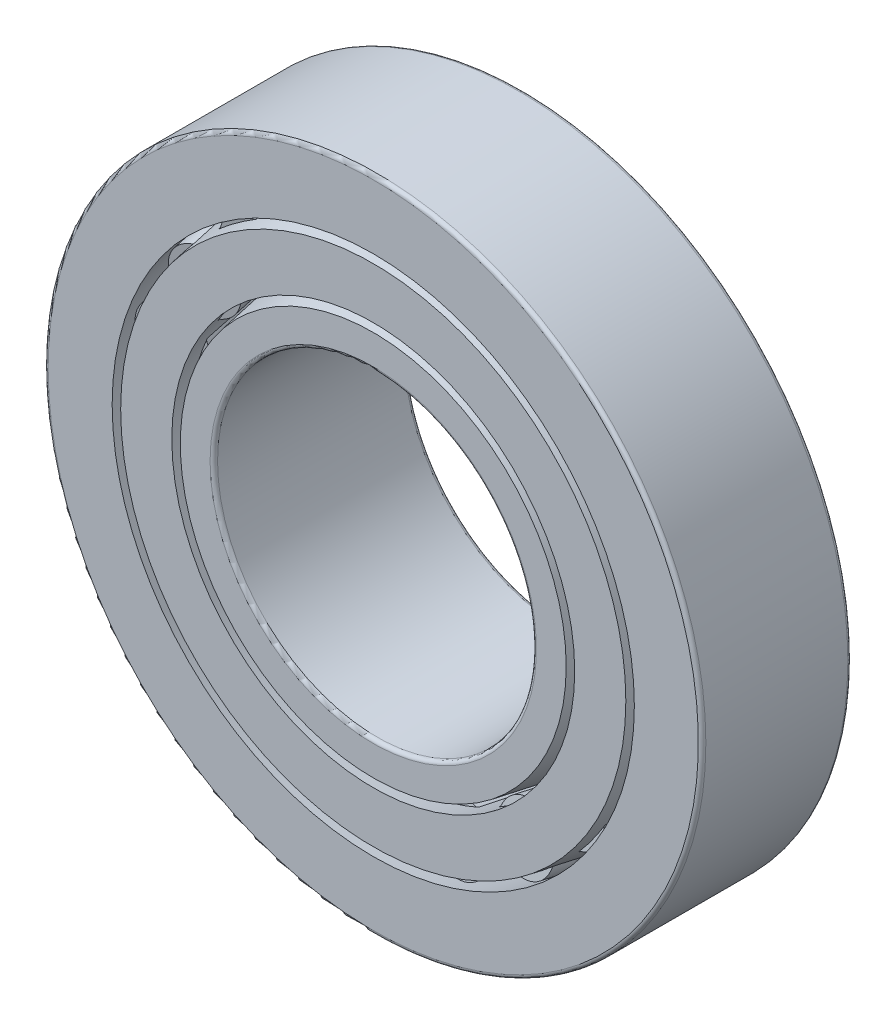
SolidWorks part; units mm, degrees
ref_plane "Front Plane" through (0, 0, 0) normal (0, 0, 1) x (1, 0, 0)
ref_plane "Top Plane" through (0, 0, 0) normal (0, 1, 0) x (1, 0, 0)
ref_plane "Right Plane" through (0, 0, 0) normal (1, 0, 0) x (0, 0, -1)
sketch "Sketch1" plane through (0, 0, 0) normal (1, 0, 0) x (0, 0, -1)
  line L0 (-15.4781, 0) -> (15.4781, 0) construction
  line L1 (0, 0) -> (0, 52.3875) construction
  line L2 (-15.4781, 25.4) -> (15.4781, 25.4) construction
  line L3 (15.4781, 25.4) -> (15.4781, 36.195) construction
  line L4 (15.4781, 36.195) -> (-15.4781, 30.7366) construction
  line L5 (-15.4781, 30.7366) -> (-15.4781, 25.4) construction
  line L7 (-15.4781, 52.3875) -> (8.3344, 52.3875)
  line L8 (8.3344, 52.3875) -> (8.3344, 45.7913)
  line L9 (8.3344, 45.7913) -> (-15.4781, 41.5925)
  line L10 (-15.4781, 41.5925) -> (-15.4781, 52.3875)
  line L11 (-15.4781, 41.5925) -> (-13.6217, 31.0639) construction
  line L12 (12.8279, 46.5836) -> (14.6844, 36.055) construction
  line L14 (-15.4781, 30.7366) -> (-13.6217, 31.0639) construction
  line L15 (-15.4781, 30.7366) -> (14.6844, 36.055) construction
  point P5 (0, 25.4)
  dimension "D1" = 100
  dimension "Width" = 30.9562
  dimension "OD" = 104.775
  dimension "Shaft Dia" = 50.8
  dimension "D2" = 26.9875
  dimension "D3" = 10.795
  dimension "Outer Wd" = 23.8125
  dimension "Bearing Wd" = 30.1625
revolve "Revolve1" add sketch "Sketch1" angle 360 about L0
sketch "Sketch5" plane through (0, 0, 0) normal (1, 0, 0) x (0, 0, -1)
  line L0 (15.4781, 36.195) -> (-15.4781, 30.7366) construction
  line L1 (15.4781, 36.195) -> (-15.4781, 30.7366)
  line L2 (-15.4781, 30.7366) -> (-15.4781, 25.4)
  line L3 (-15.4781, 25.4) -> (15.4781, 25.4)
  line L4 (15.4781, 25.4) -> (15.4781, 36.195)
revolve "Revolve4" add sketch "Sketch5" angle 360 about L0
sketch "Sketch2" plane through (0, 0, 0) normal (1, 0, 0) x (0, 0, -1)
  line L0 (-15.4781, 40.2355) -> (-15.4781, 32.0936)
  line L1 (8.3344, 44.4343) -> (13.06, 45.2675)
  line L2 (-15.4781, 32.0936) -> (8.3344, 36.2924)
  line L3 (12.8279, 46.5836) -> (14.6844, 36.055) construction
  line L4 (8.3344, 36.2924) -> (8.3344, 44.4343) construction
  line L5 (8.3344, 44.4343) -> (-15.4781, 40.2355)
  line L6 (8.3344, 45.7913) -> (-15.4781, 41.5925) construction
  line L7 (15.4781, 36.195) -> (-15.4781, 30.7366) construction
  line L8 (-15.4781, 41.5925) -> (8.3344, 45.7913) construction
  line L9 (-15.4781, 30.7366) -> (14.6844, 36.055) construction
  line L10 (13.06, 45.2675) -> (14.4523, 37.3711)
  line L11 (-15.4781, 41.5925) -> (-15.4781, 40.2355) construction
  line L12 (-15.4781, 32.0936) -> (-15.4781, 30.7366) construction
  line L13 (8.3344, 52.3875) -> (8.3344, 45.7913) construction
  line L14 (14.4523, 37.3711) -> (8.3344, 36.2924)
  dimension "D1" = 10.691
  dimension "D2" = 8.0182
revolve "Revolve2" add sketch "Sketch2" angle 360 about L0
sketch "Sketch3" plane through (0, 0, 0) normal (1, 0, 0) x (0, 0, -1)
  line L0 (-15.4781, 36.1645) -> (8.3344, 40.3633) construction
  line L1 (-15.4781, 40.2355) -> (-15.4781, 32.0936) construction
  line L2 (8.3344, 36.2924) -> (8.3344, 44.4343) construction
  line L3 (-12.6934, 36.6556) -> (-13.6217, 41.9198)
  line L5 (-13.6217, 41.9198) -> (7.4061, 45.6276)
  line L6 (7.4061, 45.6276) -> (8.3344, 40.3633)
  line L7 (8.3344, 40.3633) -> (-12.6934, 36.6556)
  line L8 (8.3344, 45.7913) -> (-15.4781, 41.5925) construction
  line L9 (-15.4781, 36.1645) -> (-14.5499, 36.3282) construction
  line L10 (-15.4781, 41.5925) -> (-13.6217, 31.0639) construction
  line L11 (-14.5499, 36.3282) -> (-13.6217, 36.4919) construction
  line L12 (-13.6217, 36.4919) -> (-12.6934, 36.6556) construction
revolve "Cut-Revolve1" cut sketch "Sketch3" angle 360 about L0
sketch "Sketch4" plane through (0, 0, 0) normal (1, 0, 0) x (0, 0, -1)
  line L0 (-13.5775, 41.6697) -> (7.4502, 45.3775)
  line L1 (7.4502, 45.3775) -> (8.3344, 40.3633)
  line L2 (8.3344, 40.3633) -> (-12.6934, 36.6556)
  line L3 (-15.4781, 36.1645) -> (-12.6934, 36.6556) construction
  line L4 (-12.6934, 36.6556) -> (-13.5775, 41.6697)
  line L6 (8.3344, 40.3633) -> (-12.6934, 36.6556) construction
  line L7 (8.3344, 45.7913) -> (-15.4781, 41.5925) construction
  dimension "D1" = 0.254
revolve "Revolve3" add sketch "Sketch4" angle 360 about L0
ref_axis "Axis1" through (0, 0, -15.4781) along (0, 0, 1)
pattern_circular "CirPattern1" count 20 over 360 about axis through (0, 0, -15.4781) along (0, 0, 1) of "Cut-Revolve1"
pattern_circular "CirPattern2" count 20 over 360 about axis through (0, 0, -15.4781) along (0, 0, 1) of bodies 403
fillet "Fillet1" radius 0.5953 2 edges at (52.3875, 0, -8.3344) (52.3875, 0, 15.4781)
fillet "Fillet2" radius 0.5953 2 edges at (25.4, 0, -15.4781) (25.4, 0, 15.4781)
sketch "Sketch6" plane through (0, 0, 0) normal (1, 0, 0) x (0, 0, -1)
  line L0 (-77.3906, 52.3875) -> (-77.3906, 41.5925)
  line L1 (-77.3906, 41.5925) -> (-53.5781, 45.7913)
  line L2 (-53.5781, 45.7913) -> (-53.5781, 52.3875)
  line L3 (-53.5781, 52.3875) -> (-77.3906, 52.3875)
  line L4 (-15.4781, 52.3875) -> (8.3344, 52.3875) construction
  line L5 (-15.4781, 41.5925) -> (-15.4781, 52.3875) construction
  line L6 (8.3344, 52.3875) -> (8.3344, 45.7913) construction
  dimension "Ring Separation" = 38.1
revolve "Revolve5" [suppressed] add sketch "Sketch6" angle 360 about L0
fillet "Fillet3" [suppressed] radius 0.5953
delete or keep bodies "Body-Delete1" [suppressed] type delete bodies bodies 399
sketch "Sketch8" plane through (0, 0, 0) normal (0, 0, 1) x (1, 0, 0)
  line L0 (0, 65.4844) -> (0, -65.4844) construction
  dimension "D1" = 130.9688
equation "\"D3@Sketch1\" = \"D2@Sketch1\"/2.5"
equation "\"D2@Sketch2\" = \"D1@Sketch2\"*.75"
equation "\"D1@Fillet1\" = \"Outer Wd@Sketch1\"*.025"
equation "\"D1@Fillet2\" = \"D1@Fillet1\""
equation "\"D1@Fillet3\" = \"D1@Fillet1\""
equation "\"Rollers@CirPattern2\" = \"D1@CirPattern1\""
equation "\"D1@Sketch8\" = \"OD@Sketch1\"*1.250"
